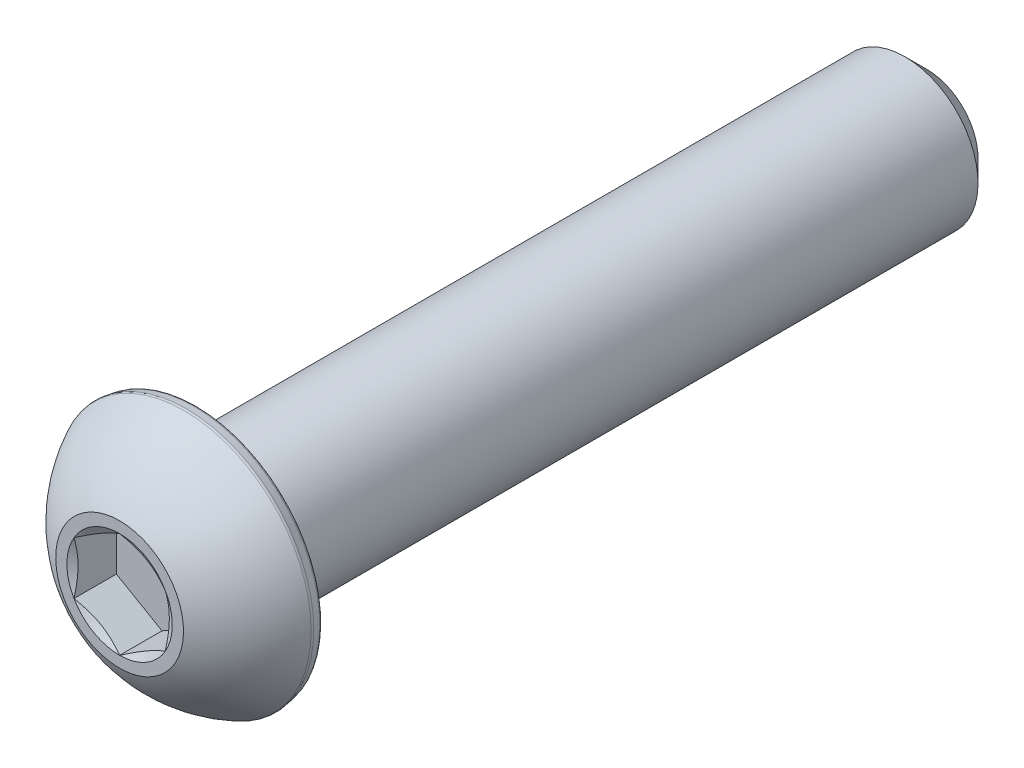
SolidWorks part; units mm, degrees
ref_plane "Front Plane" through (0, 0, 0) normal (0, 0, 1) x (1, 0, 0)
ref_plane "Top Plane" through (0, 0, 0) normal (0, 1, 0) x (1, 0, 0)
ref_plane "Right Plane" through (0, 0, 0) normal (1, 0, 0) x (0, 0, -1)
sketch "Sketch1" plane through (0, 0, 0) normal (1, 0, 0) x (0, 0, -1)
  line L0 (0, 0) -> (31.75, 0) construction
  line L1 (31.75, 3.175) -> (31.75, -3.175) construction
  line L2 (0, 0) -> (-3.3528, 0) construction
  line L3 (0, 5.5499) -> (0, -5.5499) construction
  line L4 (-3.3528, 1.9844) -> (-3.3528, -1.9844) construction
  line L5 (31.6706, 3.3125) -> (32.9406, 3.3125) construction
  line L6 (32.9406, 3.3125) -> (32.3056, 2.2126) construction
  line L7 (32.3056, 2.2126) -> (31.6706, 3.3125) construction
  line L8 (31.7103, 3.2437) -> (32.9009, 3.2437) construction
  line L9 (31.75, 3.175) -> (32.8612, 3.175) construction
  line L10 (32.2262, 2.3501) -> (32.385, 2.3501) construction
  line L11 (32.3056, 2.3501) -> (32.3056, 2.2126) construction
  line L12 (32.3056, 3.175) -> (32.3056, 3.3125) construction
  point P5 (31.75, 0)
  point P10 (-3.3528, 0)
  point P13 (0, 0)
  point P18 (28.575, -3.175)
  point P25 (32.3056, 3.2437)
  dimension "Screw Size Decimal Equivalent" = 6.35
  dimension "Length" = 31.75
  dimension "Head Diameter" = 11.0998
  dimension "Drive Size" = 3.9688
  dimension "Head Height" = 3.3528
  dimension "D1" = 60
  dimension "Pitch" = 1.27
  dimension "D2" = 0.1588
  dimension "D3" = 3.175
sketch "Sketch2" plane through (0, 0, 0) normal (1, 0, 0) x (0, 0, -1)
  line L0 (31.75, 0) -> (-3.3528, 0)
  line L1 (-3.3528, 0) -> (-3.3528, 2.7781)
  line L2 (-3.3528, 0) -> (-3.3528, 5.5499) construction
  line L3 (-3.3528, 5.5499) -> (0, 5.5499) construction
  line L4 (0, 5.4612) -> (-0.5029, 5.5499)
  line L5 (0, 5.5499) -> (0, -5.5499) construction
  line L6 (0, 5.4612) -> (0, 3.175)
  line L7 (0, 3.175) -> (30.7975, 3.175)
  line L8 (30.7975, 3.175) -> (31.75, 2.2225)
  line L9 (31.75, 3.175) -> (31.75, -3.175) construction
  line L10 (31.75, 2.2225) -> (31.75, 0)
  line L11 (-3.3528, 0) -> (-3.3528, -2.7781) construction
  arc A0 (-0.5029, 5.5499) -> (-3.3528, 2.7781) centre (2.122, 0) ccw
  dimension "D1" = 45
  dimension "D2" = 0.9525
  dimension "D3" = 10
  dimension "D4" = 0.5029
  dimension "D5" = 5.5563
revolve "Revolve1" add sketch "Sketch2" angle 360 about L0
sketch "Sketch3" plane through (0, 0, 3.3528) normal (0, 0, 1) x (1, 0, 0)
  line L1 (0, 2.2914) -> (-1.9844, 1.1457)
  line L2 (-1.9844, 1.1457) -> (-1.9844, -1.1457)
  line L3 (-1.9844, -1.1457) -> (0, -2.2914)
  line L4 (0, -2.2914) -> (1.9844, -1.1457)
  line L5 (1.9844, -1.1457) -> (1.9844, 1.1457)
  line L6 (1.9844, 1.1457) -> (0, 2.2914)
  circle A0 centre (0, 0) radius 1.9844 construction
extrude "Cut-Extrude1" cut sketch "Sketch3" against normal blind 1.844
sketch "Sketch4" plane through (0, 0, 3.3528) normal (0, 0, 1) x (1, 0, 0)
  circle A0 centre (0, 0) radius 2.2914
extrude "Cut-Extrude2" cut sketch "Sketch4" against normal blind 1.844 draft 60
fillet "Fillet1" radius 0.1676 2 edges at (0, 5.5499, 0.5029) (0, 5.4612, 0)
sketch "Sketch8" plane through (0, 0, 0) normal (0, 0, 1) x (1, 0, 0)
  circle A0 centre (0, 0) radius 5.5499 construction
  circle A1 centre (0, 0) radius 1.9844 construction
ref_plane "Plane1" [suppressed] through (0, 0, -0.5715) normal (0, 0, 1) x (1, 0, 0)
split "Split1" [suppressed] bodies to split 106
sketch "Sketch5" [suppressed] plane through (0, 0, 0) normal (1, 0, 0) x (0, 0, -1)
  line L0 (31.7103, 3.2437) -> (32.9009, 3.2437)
  line L1 (32.9009, 3.2437) -> (32.385, 2.3501)
  line L2 (32.385, 2.3501) -> (32.2262, 2.3501)
  line L3 (32.2262, 2.3501) -> (31.7103, 3.2437)
sketch "Sketch6" [suppressed] plane through (0, 0, -31.75) normal (0, 0, -1) x (-1, 0, 0)
  circle A0 centre (0, 0) radius 3.175
curve "Helix/Spiral1" [suppressed] pitch 1.27 height 33.02 turns 26
sweep "Cut-Sweep1" [suppressed] cut profiles "Sketch5" path "Helix/Spiral1"
combine bodies "Combine1" [suppressed] operation type add bodies to combine 109 107
sketch "Sketch7" [suppressed] plane through (0, 0, -0.5715) normal (0, 0, 1) x (1, 0, 0)
  circle A0 centre (0, 0) radius 3.175
extrude "Boss-Extrude1" [suppressed] add sketch "Sketch7" against normal blind 3.175 draft 45
fillet "Fillet2" [suppressed] radius 0.1676
equation "\"D2@Sketch1\"=\"Pitch@Sketch1\"/8"
equation "\"D2@Sketch2\"=\"Pitch@Sketch1\"*.75"
equation "\"D4@Sketch2\"=\"Head Height@Sketch1\"*.15"
equation "\"D5@Sketch2\"=\"Drive Size@Sketch1\"*1.4"
equation "\"D1@Cut-Extrude1\"=\"Head Height@Sketch1\"*.55"
equation "\"D1@Cut-Extrude2\"=\"D1@Cut-Extrude1\""
equation "\"D1@Fillet1\"=\"Head Height@Sketch1\"*.05"
equation "\"D4@Helix/Spiral1\"=\"Pitch@Sketch1\""
equation "\"D3@Helix/Spiral1\"=\"Length@Sketch1\"+\"Pitch@Sketch1\""
equation "\"D3@Sketch1\"=\"Pitch@Sketch1\"*2.5"
equation "\"D1@Fillet2\"=\"D1@Fillet1\""
equation "\"D1@Plane1\"=\"Pitch@Sketch1\"*.45"
equation "\"D1@Boss-Extrude1\"=\"Pitch@Sketch1\"*2.5"
